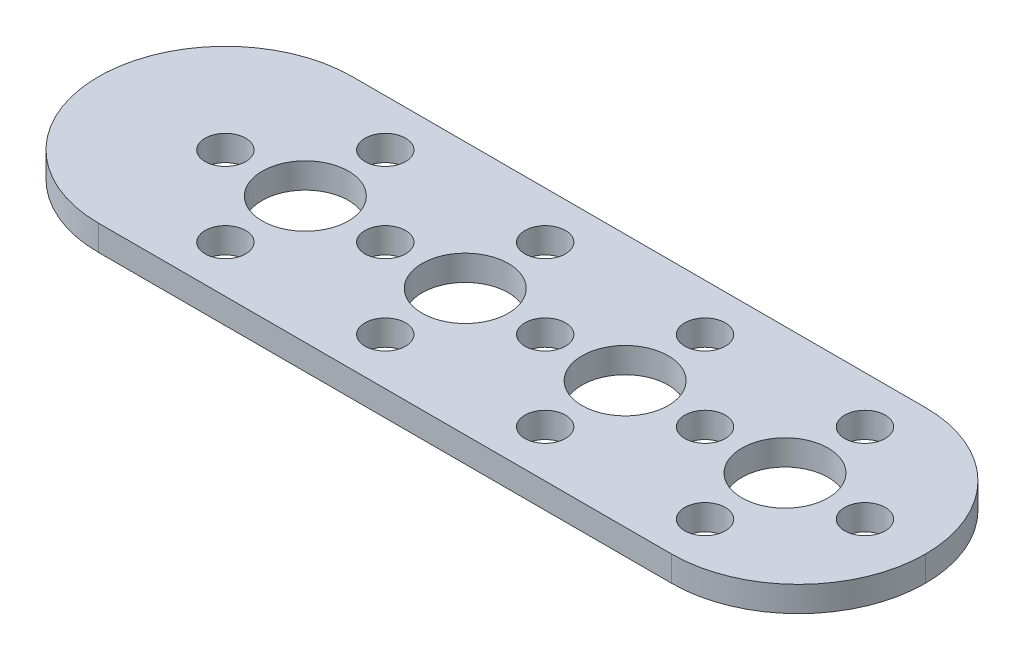
SolidWorks part; units mm, degrees
ref_plane "Front Plane" through (0, 0, 0) normal (0, 0, 1) x (1, 0, 0)
ref_plane "Top Plane" through (0, 0, 0) normal (0, 1, 0) x (1, 0, 0)
ref_plane "Right Plane" through (0, 0, 0) normal (1, 0, 0) x (0, 0, -1)
sketch "Sketch2" plane through (0, 0, 0) normal (0, 1, 0) x (1, 0, 0)
  line L0 (56.007, 12.7) -> (62.0618, 12.7)
  line L1 (-8.001, 12.7) -> (56.007, 12.7)
  line L2 (62.0618, 12.7) -> (62.0618, -12.7)
  line L3 (-8.001, -12.7) -> (56.007, -12.7)
  line L4 (62.0618, -12.7) -> (56.007, -12.7)
  circle A0 centre (0, 0) radius 4.318
  circle A1 centre (0, -8.001) radius 2.032
  circle A2 centre (-8.001, 0) radius 2.032
  circle A3 centre (0, 8.001) radius 2.032
  circle A4 centre (8.001, 0) radius 2.032
  circle A5 centre (16.002, -8.001) radius 2.032
  circle A6 centre (16.002, 0) radius 4.318
  circle A7 centre (24.003, 0) radius 2.032
  circle A8 centre (16.002, 8.001) radius 2.032
  circle A9 centre (8.001, 0) radius 2.032
  circle A10 centre (32.004, -8.001) radius 2.032
  circle A11 centre (32.004, 0) radius 4.318
  circle A12 centre (40.005, 0) radius 2.032
  circle A13 centre (32.004, 8.001) radius 2.032
  circle A14 centre (24.003, 0) radius 2.032
  circle A15 centre (48.006, -8.001) radius 2.032
  circle A16 centre (48.006, 0) radius 4.318
  circle A17 centre (56.007, 0) radius 2.032
  circle A18 centre (48.006, 8.001) radius 2.032
  circle A19 centre (40.005, 0) radius 2.032
  arc A20 (-8.001, 12.7) -> (-8.001, -12.7) centre (-8.001, 0) ccw
  point P14 (0, 0)
  dimension "D1" = 8.001
  dimension "D4" = 8.001
  dimension "D5" = 8.001
  dimension "D6" = 25.4
  dimension "D7" = 12.7
  dimension "D3" = 4
  dimension "D2" = 4
extrude "Boss-Extrude1" add sketch "Sketch2" along normal blind 2.54
fillet "Fillet1" radius 12.7 2 edges at (62.0618, 1.27, 12.7) (62.0618, 1.27, -12.7)
